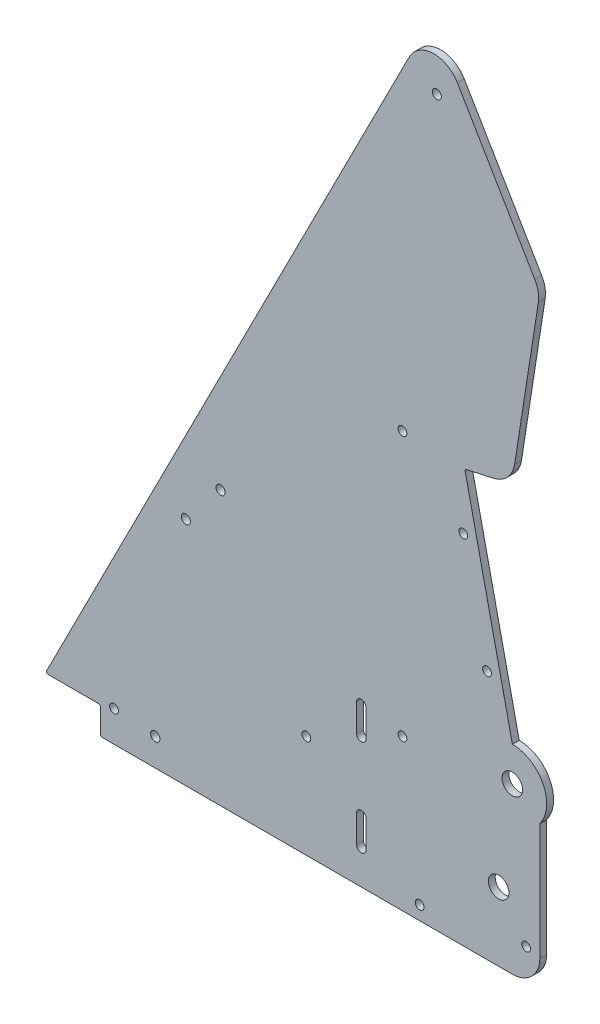
SolidWorks part; units mm, degrees
other "Markup1"
sketch "Sketch5"
ref_plane "Front Plane" through (0, 0, 0) normal (0, 0, 1) x (1, 0, 0)
ref_plane "Top Plane" through (0, 0, 0) normal (0, 1, 0) x (1, 0, 0)
ref_plane "Right Plane" through (0, 0, 0) normal (1, 0, 0) x (0, 0, -1)
sketch "Sketch1" plane through (0, 0, 0) normal (0, 0, 1) x (1, 0, 0)
  line L1 (228.6, -12.7) -> (228.6, 53.975)
  line L2 (178.7547, 351.4131) -> (0, 0)
  line L3 (228.6, 266.7) -> (178.7547, 351.4131)
  line L5 (0, 0) -> (25.4, 0)
  line L6 (25.4, 0) -> (25.4, -12.7)
  line L7 (25.4, -12.7) -> (228.6, -12.7)
  line L9 (215.9, 79.375) -> (193.9097, 178.5667)
  line L10 (193.9097, 178.5667) -> (215.6079, 183.377)
  line L11 (215.6079, 183.377) -> (228.6, 266.7)
  arc A0 (228.6, 53.975) -> (215.9, 79.375) centre (215.9, 63.5) ccw
  dimension "D7" = 12.7
  dimension "D8" = 76.2
  dimension "D10" = 31.75
  dimension "D2" = 279.4
  dimension "D3" = 25.4
  dimension "D4" = 215.9
  dimension "D5" = 394.2644
  dimension "D6" = 203.2
  dimension "D9" = 63.039
  dimension "D11" = 101.6
  dimension "D12" = 12.5
  dimension "D13" = 22.225
extrude "Boss-Extrude1" add sketch "Sketch1" along normal blind 3.175
sketch "Sketch2" plane through (0, 0, 3.175) normal (0, 0, 1) x (1, 0, 0)
  line L0 (178.7547, 351.4131) -> (0, 0) construction
  line L1 (25.4, -12.7) -> (228.6, -12.7) construction
  line L2 (215.9, 79.375) -> (193.9097, 178.5667) construction
  line L3 (193.9097, 178.5667) -> (215.6079, 183.377) construction
  line L4 (215.9, 79.375) -> (193.9097, 178.5667) construction
  line L10 (228.6, -12.7) -> (228.6, 53.975) construction
  circle A0 centre (64.9432, 94.0578) radius 2.0955
  circle A1 centre (180.975, 322.1643) radius 2.0955
  circle A2 centre (81.0071, 113.733) radius 2.0955
  circle A3 centre (193.2078, 152.3944) radius 2.032
  circle A4 centre (215.9, 63.5) radius 4.7625
  circle A7 centre (173.0375, -6.35) radius 2.032
  circle A8 centre (204.203, 102.7985) radius 2.032
  circle A26 centre (209.55, 19.05) radius 4.7625
  arc A30 (228.6, 53.975) -> (215.9, 79.375) centre (215.9, 63.5) ccw construction
  circle A31 centre (165.1, 179.3875) radius 2.032
  dimension "D3" = 4.191
  dimension "D5" = 4.191
  dimension "D9" = 4.191
  dimension "D20" = 9.525
  dimension "D23" = 9.525
  dimension "D18" = 4.064
  dimension "D26" = 4.064
  dimension "D14" = 4.064
  dimension "D2" = 15.24
  dimension "D6" = 15.24
  dimension "D7" = 25.4
  dimension "D8" = 20.6375
  dimension "D21" = 44.45
  dimension "D22" = 6.35
  dimension "D19" = 160.3375
  dimension "D24" = 44.45
  dimension "D25" = 6.35
  dimension "D27" = 25.4
  dimension "D28" = 50.8
  dimension "D29" = 6.35
  dimension "D17" = 6.35
  dimension "D33" = 55.5625
  dimension "D15" = 114.3
  dimension "D4" = 180.975
extrude "Cut-Extrude1" cut sketch "Sketch2" against normal through all
sketch "Sketch7" plane through (0, 0, 3.175) normal (0, 0, 1) x (1, 0, 0)
  line L0 (146.05, 3.175) -> (146.05, 15.875) construction
  line L1 (143.891, 3.175) -> (143.891, 15.875)
  line L2 (148.209, 3.175) -> (148.209, 15.875)
  line L3 (146.05, 47.625) -> (146.05, 60.325) construction
  line L4 (143.891, 47.625) -> (143.891, 60.325)
  line L5 (148.209, 47.625) -> (148.209, 60.325)
  line L6 (25.4, -12.7) -> (228.6, -12.7) construction
  line L12 (228.6, -12.7) -> (228.6, 53.975) construction
  line L13 (25.4, -12.7) -> (228.6, -12.7) construction
  arc A0 (143.891, 3.175) -> (148.209, 3.175) centre (146.05, 3.175) ccw
  arc A1 (148.209, 15.875) -> (143.891, 15.875) centre (146.05, 15.875) ccw
  arc A2 (143.891, 47.625) -> (148.209, 47.625) centre (146.05, 47.625) ccw
  arc A3 (148.209, 60.325) -> (143.891, 60.325) centre (146.05, 60.325) ccw
  circle A8 centre (50.8, 0) radius 2.159
  point P2 (146.05, 9.525)
  point P9 (146.05, 53.975)
  dimension "D1" = 4.318
  dimension "D5" = 4.318
  dimension "D2" = 12.7
  dimension "D3" = 12.7
  dimension "D4" = 44.45
  dimension "D6" = 95.25
  dimension "D7" = 82.55
  dimension "D8" = 15.875
  dimension "D9" = 12.7
extrude "Cut-Extrude2" cut sketch "Sketch7" against normal through all
sketch "Sketch10" plane through (0, 0, 3.175) normal (0, 0, 1) x (1, 0, 0)
  circle A1 centre (165.1, 57.15) radius 2.032
  circle A2 centre (120.65, 34.925) radius 2.032
  dimension "D1" = 4.064
  dimension "D4" = 63.5
  dimension "D5" = 69.85
extrude "Cut-Extrude3" cut sketch "Sketch10" against normal up to next
fillet "Fillet1" radius 12.7 4 edges at (228.6, -12.7, 1.5875) (178.7547, 351.4131, 1.5875) (215.6079, 183.377, 1.5875) (228.6, 266.7, 1.5875)
fillet "Fillet2" radius 0.7937 4 edges at (25.4, -12.7, 1.5875) (25.4, 0, 1.5875) (193.9097, 178.5667, 1.5875) (0, 0, 1.5875)
sketch "Sketch12" plane through (0, 0, 3.175) normal (0, 0, 1) x (1, 0, 0)
  circle A0 centre (31.75, 1.5875) radius 2.032
  circle A1 centre (222.25, 1.5875) radius 2.032
  dimension "D1" = 4.064
extrude "Cut-Extrude5" cut sketch "Sketch12" against normal through all
equation "\"D6@Sketch2\"=\"D2@Sketch2\""
